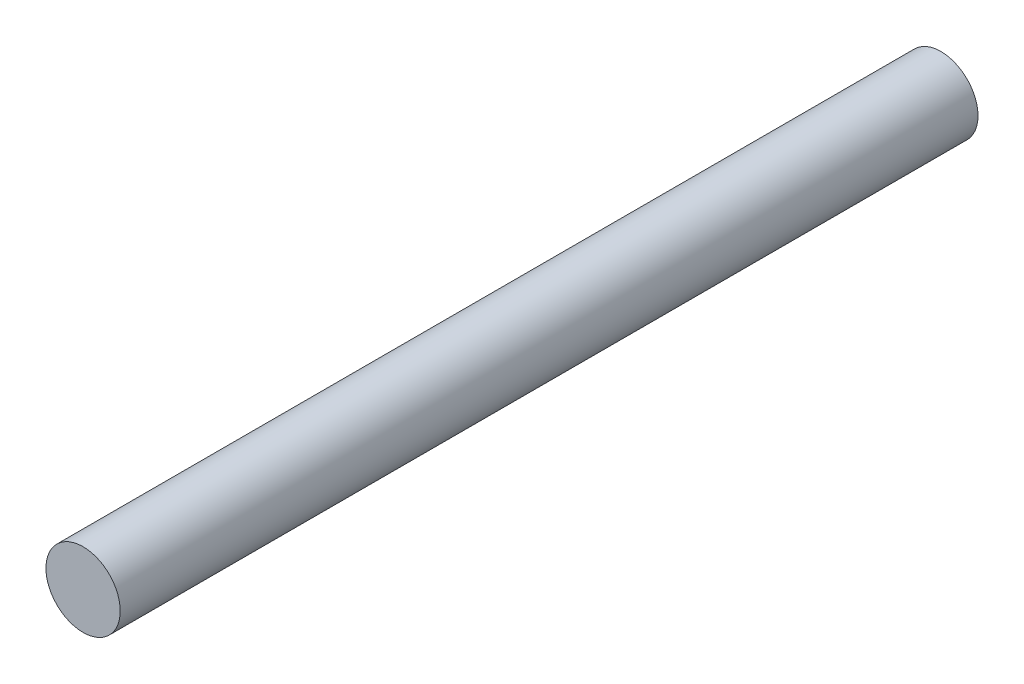
SolidWorks part; units mm, degrees
ref_plane "Front Plane" through (0, 0, 0) normal (0, 0, 1) x (1, 0, 0)
ref_plane "Top Plane" through (0, 0, 0) normal (0, 1, 0) x (1, 0, 0)
ref_plane "Right Plane" through (0, 0, 0) normal (1, 0, 0) x (0, 0, -1)
sketch "Sketch1" plane through (0, 0, 0) normal (0, 0, 1) x (1, 0, 0)
  circle A0 centre (0, 0) radius 5.5
  dimension "D1" = 11
extrude "Boss-Extrude1" add sketch "Sketch1" along normal mid plane 127
